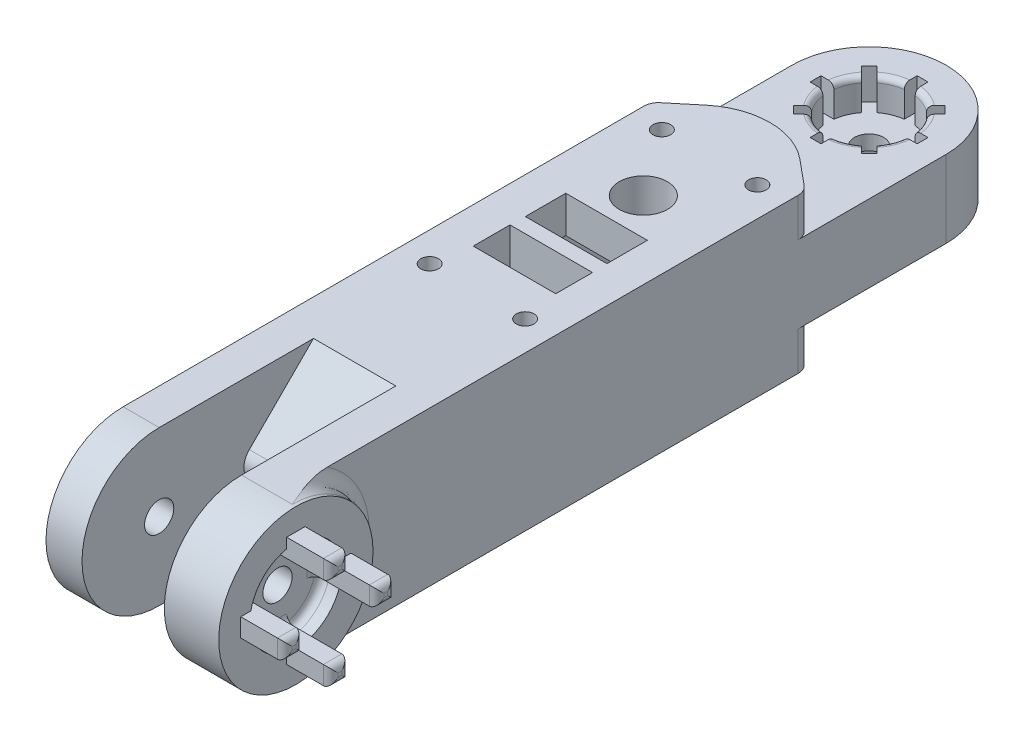
SolidWorks part; units mm, degrees
ref_plane "Front Plane" through (0, 0, 0) normal (0, 0, 1) x (1, 0, 0)
ref_plane "Top Plane" through (0, 0, 0) normal (0, 1, 0) x (1, 0, 0)
ref_plane "Right Plane" through (0, 0, 0) normal (1, 0, 0) x (0, 0, -1)
sketch "Sketch1" plane through (0, 0, 0) normal (0, 0, 1) x (1, 0, 0)
  line L1 (-21, 21) -> (21, 21)
  line L2 (-21, 21) -> (-21, -21)
  line L3 (-21, -21) -> (21, -21)
  line L4 (21, 21) -> (21, -21)
  line L5 (-21, 21) -> (21, -21) construction
  line L6 (-21, -21) -> (21, 21) construction
  point P0 (0, 0)
  dimension "D1" = 42
  dimension "D2" = 42
extrude "Boss-Extrude1" add sketch "Sketch1" along normal blind 140
ref_plane "Plane1" through (0, 0, 140) normal (0, 0, 1) x (1, 0, 0)
sketch "Sketch2" plane through (0, 0, 140) normal (0, 0, 1) x (1, 0, 0)
  line L0 (-21, -21) -> (21, -21) construction
  line L1 (-21, 21) -> (-11.2, 21)
  line L2 (-21, 21) -> (-21, -21)
  line L3 (-21, -21) -> (-11.2, -21)
  line L4 (-11.2, 21) -> (-11.2, -21)
  line L5 (21, 21) -> (-21, 21) construction
  line L6 (21, -21) -> (11.2, -21)
  line L7 (21, -21) -> (21, 21)
  line L8 (21, 21) -> (11.2, 21)
  line L9 (11.2, -21) -> (11.2, 21)
  dimension "D1" = 9.8
  dimension "D2" = 9.8
extrude "Boss-Extrude2" add sketch "Sketch2" along normal blind 21
ref_plane "Plane2" through (-11.2, 0, 0) normal (1, 0, 0) x (0, 0, -1)
sketch "Sketch3" plane through (-11.2, 0, 0) normal (1, 0, 0) x (0, 0, -1)
  line L0 (-161, -21) -> (-161, 21)
  arc A0 (-161, -21) -> (-161, 21) centre (-161, 0) cw
  dimension "D1" = 21
ref_plane "Plane3" through (0, -21, 0) normal (0, -1, 0) x (-1, 0, 0)
ref_plane "Plane4" through (11.2, 0, 0) normal (-1, 0, 0) x (0, 0, 1)
sketch "Sketch5" plane through (11.2, 0, 0) normal (-1, 0, 0) x (0, 0, 1)
  line L0 (161, 21) -> (161, -21)
  line L4 (140, 21) -> (140, -21)
  line L5 (140, -21) -> (161, -21)
  line L6 (161, -21) -> (161, 21)
  line L7 (161, 21) -> (140, 21)
  line L8 (140, 21) -> (140, -21)
  line L9 (140, -21) -> (161, -21)
  line L11 (161, 21) -> (140, 21)
  arc A0 (161, 21) -> (161, -21) centre (161, 0) cw
  dimension "D1" = 21
  dimension "D2" = 0
extrude "Boss-Extrude4" add sketch "Sketch5" against normal blind 9.8 contours A0 L0 region at (11.2, 0, 169.9127)
extrude "Boss-Extrude5" add sketch "Sketch3" against normal blind 9.8
sketch "Sketch6" plane through (11.2, 0, 0) normal (-1, 0, 0) x (0, 0, 1)
  line L0 (161, -21) -> (161, 21) construction
  circle A0 centre (161, 0) radius 3.975
  dimension "D1" = 7.95
extrude "Cut-Extrude1" cut sketch "Sketch6" against normal through all
ref_plane "Plane5" through (-11.2, 0, 0) normal (1, 0, 0) x (0, 0, -1)
sketch "Sketch8" plane through (-11.2, 0, 0) normal (1, 0, 0) x (0, 0, -1)
  line L0 (-161, -21) -> (-161, 21) construction
  circle A0 centre (-161, 0) radius 3.975
  dimension "D1" = 7.95
extrude "Cut-Extrude2" cut sketch "Sketch8" against normal through all
ref_plane "Plane6" through (0, 0, 0) normal (0, 0, -1) x (-1, 0, 0)
sketch "Sketch9" plane through (0, 0, 0) normal (0, 0, -1) x (-1, 0, 0)
  line L0 (21, 21) -> (21, -21) construction
  line L1 (21, 10.5) -> (-21, 10.5)
  line L2 (21, 10.5) -> (21, -10.5)
  line L3 (21, -10.5) -> (-21, -10.5)
  line L4 (-21, 10.5) -> (-21, -10.5)
  line L5 (-21, -21) -> (-21, 21) construction
  line L6 (-21, 21) -> (21, 21) construction
  line L7 (21, -21) -> (-21, -21) construction
  dimension "D1" = 10.5
  dimension "D2" = 10.5
extrude "Boss-Extrude6" add sketch "Sketch9" along normal blind 21
ref_plane "Plane7" through (0, -10.5, 0) normal (0, -1, 0) x (-1, 0, 0)
sketch "Sketch10" plane through (0, -10.5, 0) normal (0, -1, 0) x (-1, 0, 0)
  line L0 (-21, 21) -> (21, 21)
  arc A0 (-21, 21) -> (21, 21) centre (0, 21) cw
  dimension "D1" = 21
extrude "Boss-Extrude7" add sketch "Sketch10" against normal blind 21
sketch "Sketch11" plane through (0, -10.5, 0) normal (0, -1, 0) x (-1, 0, 0)
  line L0 (21, 21) -> (-21, 21) construction
  circle A0 centre (0, 21) radius 11.35
  dimension "D1" = 22.7
extrude "Cut-Extrude3" cut sketch "Sketch11" against normal blind 8.5
ref_plane "Plane8" through (11.2, 0, 0) normal (-1, 0, 0) x (0, 0, 1)
sketch "Sketch16" plane through (11.2, 0, 0) normal (-1, 0, 0) x (0, 0, 1)
  line L0 (140, 21) -> (140, 0)
  line L1 (140, 21) -> (140, -21) construction
  line L2 (140, 0) -> (140, -21)
  line L3 (140, -21) -> (119, -21)
  line L4 (119, -21) -> (140, 0)
  line L5 (140, 21) -> (119, 21)
  line L6 (119, 21) -> (140, 0)
  line L7 (161, 0) -> (140, 0) construction
  dimension "D1" = 21
  dimension "D2" = 21
extrude "Cut-Extrude4" cut sketch "Sketch16" along normal blind 22.4 contours L0 L5 L6 | L2 L3 L4
fillet "Fillet1" radius 5 1 edges at (0, 0, 140)
ref_plane "Plane9" through (0, -10.5, 0) normal (0, -1, 0) x (-1, 0, 0)
ref_plane "Plane10" through (0, 10.5, 0) normal (0, 1, 0) x (1, 0, 0)
sketch "Sketch18" plane through (0, 10.5, 0) normal (0, 1, 0) x (1, 0, 0)
  line L0 (21, 21) -> (-21, 21) construction
  circle A0 centre (0, 21) radius 11.1605
  dimension "D1" = 22.321
extrude "Cut-Extrude5" cut sketch "Sketch18" against normal blind 8.5
sketch "Sketch19" plane through (0, -2, 0) normal (0, -1, 0) x (1, 0, 0)
  circle A0 centre (0, -21) radius 3.975
  dimension "D1" = 7.95
extrude "Cut-Extrude6" cut sketch "Sketch19" against normal blind 8.5
fillet "Fillet4" radius 1.5 1 edges at (11.35, -10.5, -21)
fillet "Fillet5" radius 1.5 1 edges at (-11.1605, 10.5, -21)
sketch "Sketch20" plane through (0, 10.5, 0) normal (0, 1, 0) x (1, 0, 0)
  line L1 (-1.48, 35.5655) -> (1.48, 35.5655)
  line L2 (-1.48, 35.5655) -> (-1.48, 31.7555)
  line L3 (-1.48, 31.7555) -> (1.48, 31.7555)
  line L4 (1.48, 35.5655) -> (1.48, 31.7555)
  line L5 (-1.48, 35.5655) -> (1.48, 31.7555) construction
  line L6 (-1.48, 31.7555) -> (1.48, 35.5655) construction
  circle A0 centre (0, 21) radius 12.6605 construction
  point P0 (0, 33.6605)
  dimension "D1" = 2.96
  dimension "D2" = 3.81
extrude "Cut-Extrude7" cut sketch "Sketch20" against normal blind 8.5
pattern_circular "CirPattern1" count 8 over 360 about axis through (0, 2, -21) along (0, 1, 0) of "Cut-Extrude7"
ref_plane "Plane11" through (0, 0, 0) normal (0, 1, 0) x (1, 0, 0)
mirror "Mirror1" about plane through (0, 0, 0) normal (0, 1, 0) of "CirPattern1"
sketch "Sketch25" plane through (0, -21, 0) normal (0, -1, 0) x (1, 0, 0)
  line L0 (0, 0) -> (0, 119) construction
  line L2 (-21, 0) -> (21, 0) construction
  line L3 (17, 78.5) -> (-17, 78.5)
  line L4 (17, 78.5) -> (17, 29.5)
  line L5 (17, 29.5) -> (-17, 29.5)
  line L6 (-17, 78.5) -> (-17, 29.5)
  line L7 (17, 78.5) -> (-17, 29.5) construction
  line L8 (17, 29.5) -> (-17, 78.5) construction
  point P5 (0, 54)
  dimension "D1" = 34
  dimension "D2" = 49
  dimension "D3" = 54
extrude "Cut-Extrude11" cut sketch "Sketch25" against normal blind 32 contours L3 L6 L5 L4 region at (0, -21, 54)
sketch "Sketch26" plane through (0, -21, 0) normal (0, -1, 0) x (1, 0, 0)
  line L0 (0, 29.5) -> (0, 18.4) construction
  line L1 (17, 29.5) -> (-17, 29.5)
  line L2 (17, 29.5) -> (17, 26.5)
  line L3 (17, 26.5) -> (-17, 26.5)
  line L4 (-17, 29.5) -> (-17, 26.5)
  line L5 (-17, 26.5) -> (17, 26.5)
  line L6 (-17, 26.5) -> (-17, 18.4)
  line L7 (-17, 18.4) -> (17, 18.4)
  line L8 (17, 26.5) -> (17, 18.4)
  line M6 (17, 29.5) -> (-17, 29.5)
  line M7 (-21, 0) -> (21, 0)
  dimension "D1" = 3
  dimension "D2" = 8.1
extrude "Cut-Extrude12" cut sketch "Sketch26" against normal blind 27 contours L3 L0 L8 M7 | L0 L3 L2 M6 | L0 L1 L4 L5 | L0 L5 L6 M7 | L0 L6 L7 M7 | L0 L7 L8 M7 region at (8.5, -21, 28) region at (-8.5, -21, 28) region at (8.5, -21, 22.45) region at (-8.5, -21, 22.45)
sketch "Sketch30" plane through (0, 6, 0) normal (0, -1, 0) x (1, 0, 0)
  line L0 (0, 29.5) -> (0, 18.4) construction
  line L1 (17, 29.5) -> (-17, 29.5) construction
  line L2 (-17, 18.4) -> (17, 18.4) construction
  line L3 (-17, 29.5) -> (-17, 18.4) construction
  circle A0 centre (-13, 22.4) radius 4
  circle A1 centre (-13, 22.4) radius 2.4
  dimension "D1" = 8
  dimension "D2" = 4.8
extrude "Cut-Extrude13" cut sketch "Sketch30" against normal through all contours A1 region at (-13, 6, 22.4)
ref_plane "Plane12" through (0, 0, 0) normal (-1, 0, 0) x (0, 0, 1)
mirror "Mirror9" about plane through (0, 0, 0) normal (-1, 0, 0) of "Cut-Extrude13"
ref_plane "Plane13" through (0, 0, 54) normal (0, 0, 1) x (1, 0, 0)
sketch "Sketch32" plane through (0, 21, 0) normal (0, 1, 0) x (1, 0, 0)
  line L3 (0, 0) -> (0, -65.7087) construction
  line L4 (0, 17.6) -> (0, -17.6) construction
  line L10 (0, 0) -> (21, -17.4215)
  line L11 (21, -161) -> (21, 0) construction
  line L13 (-21, -161) -> (-21, 0) construction
  line L14 (-21, -17.4215) -> (0, 0)
  line L15 (0, 0) -> (-21, 0)
  line L16 (-21, 0) -> (-21, -17.4215)
  line L17 (0, 0) -> (21, 0)
  line L18 (21, 0) -> (21, -17.4215)
  line M13 (21, -161) -> (21, 0)
  line M14 (21, 0) -> (-21, 0)
  line M15 (-21, 0) -> (-21, -161)
fillet "Fillet10" radius 3 2 edges at (-17, -7.5, 18.4) (17, -7.5, 18.4)
ref_plane "Plane14" through (0, 0, 54) normal (0, 0, -1) x (-1, 0, 0)
mirror "Mirror12" about plane through (0, 0, 54) normal (0, 0, -1) of "Fillet10", "Mirror9", "Cut-Extrude13", "Cut-Extrude12"
extrude "Cut-Extrude16" cut sketch "Sketch32" against normal blind 10.5 contours L14 M15 M14 | L10 M14 M13 region at (14, 21, 5.8072) region at (-14, 21, 5.8072)
fillet "Fillet12" radius 20 1 edges at (0, 15.75, 0)
mirror "Mirror13" about plane through (0, 0, 0) normal (0, 1, 0) of "Fillet12", "Cut-Extrude16"
fillet "Fillet13" radius 4 4 edges at (-21, 15.75, 17.4215) (-21, -15.75, 17.4215) (21, -15.75, 17.4215) (21, 15.75, 17.4215)
sketch "Sketch33" plane through (0, 11, 0) normal (0, -1, 0) x (1, 0, 0)
  line L0 (-17, 78.5) -> (-17, 65.5) construction
  line L1 (-17, 78.5) -> (-17, 29.5) construction
  line L2 (0, 78.5) -> (0, 29.5) construction
  line L3 (17, 78.5) -> (-17, 78.5) construction
  line L4 (17, 29.5) -> (-17, 29.5) construction
  line L5 (-17, 65.5) -> (17, 65.5) construction
  line L7 (17, 86.6) -> (17, 21.4) construction
  line L8 (-11.225, 65.5) -> (11.225, 65.5)
  line L9 (-11.225, 65.5) -> (-11.225, 75.5)
  line L10 (-11.225, 75.5) -> (11.225, 75.5)
  line L11 (11.225, 75.5) -> (11.225, 65.5)
  line L12 (-17, 47) -> (17, 47) construction
  line L13 (17, 78.5) -> (17, 29.5) construction
  line L15 (11.1, 50.44) -> (-11.1, 50.44)
  line L16 (11.1, 50.44) -> (11.1, 61.44)
  line L17 (11.1, 61.44) -> (-11.1, 61.44)
  line L18 (-11.1, 50.44) -> (-11.1, 61.44)
  circle A0 centre (0, 40.44) radius 6.56
  point P12 (0, 29.5)
  point P17 (0, 65.5)
  point P26 (0, 50.44)
  dimension "D5" = 13.12
  dimension "D1" = 13
  dimension "D2" = 22.45
  dimension "D3" = 10
  dimension "D4" = 17.5
  dimension "D6" = 21
  dimension "D7" = 22.2
  dimension "D8" = 11
extrude "Cut-Extrude17" cut sketch "Sketch33" against normal through all
sketch "Sketch34" plane through (21, 0, 0) normal (1, 0, 0) x (0, 0, -1)
  line L8 (-176, 2.5) -> (-171, 2.5)
  line L9 (-176, 2.5) -> (-176, -2.5)
  line L10 (-176, -2.5) -> (-171, -2.5)
  line L11 (-171, 2.5) -> (-171, -2.5)
  line L12 (-176, 2.5) -> (-171, -2.5) construction
  line L13 (-176, -2.5) -> (-171, 2.5) construction
  circle A0 centre (-161, 0) radius 12.5
  circle A1 centre (-161, 0) radius 21
  arc A2 (-161, 21) -> (-161, -21) centre (-161, 0) ccw construction
  point P3 (-173.5, 0)
  point P4 (-173.5, 0)
  arc M9 (-161, 21) -> (-161, -21) centre (-161, 0) ccw
  dimension "D1" = 25
  dimension "D2" = 5
  dimension "D3" = 5
extrude "Boss-Extrude8" add sketch "Sketch34" along normal blind 17 contours A0 L8 L9 L10 | L8 A0 L10 L11 region at (21, 0, 174.707) region at (21, 0, 172.2092)
fillet "Fillet14" radius 2 4 edges at (38, 2.5, 173.5) (38, 0, 176) (38, -2.5, 173.5) (38, 0, 171)
pattern_circular "CirPattern2" count 4 over 360 about axis through (21, 0, 161) along (-1, 0, 0) of "Boss-Extrude8", "Fillet14"
extrude "Boss-Extrude9" add sketch "Sketch34<4>" along normal blind 5 contours A1 A0 L10 L9 L8 M9 region at (21, -14.4292, 146.5708)
sketch "Sketch34<4>" plane through (21, 0, 0) normal (1, 0, 0) x (0, 0, -1) same geometry as "Sketch34"
fillet "Fillet16" radius 2 8 edges at (21, 0, 171) (21, -8.8388, 169.8388) (21, -10, 161) (21, -8.8388, 152.1612) (21, 10, 161) (21, 8.8388, 169.8388) (21, 8.8388, 152.1612) (21, 0, 151)
fillet "Fillet18" radius 4 1 edges at (21, 0, 140)
